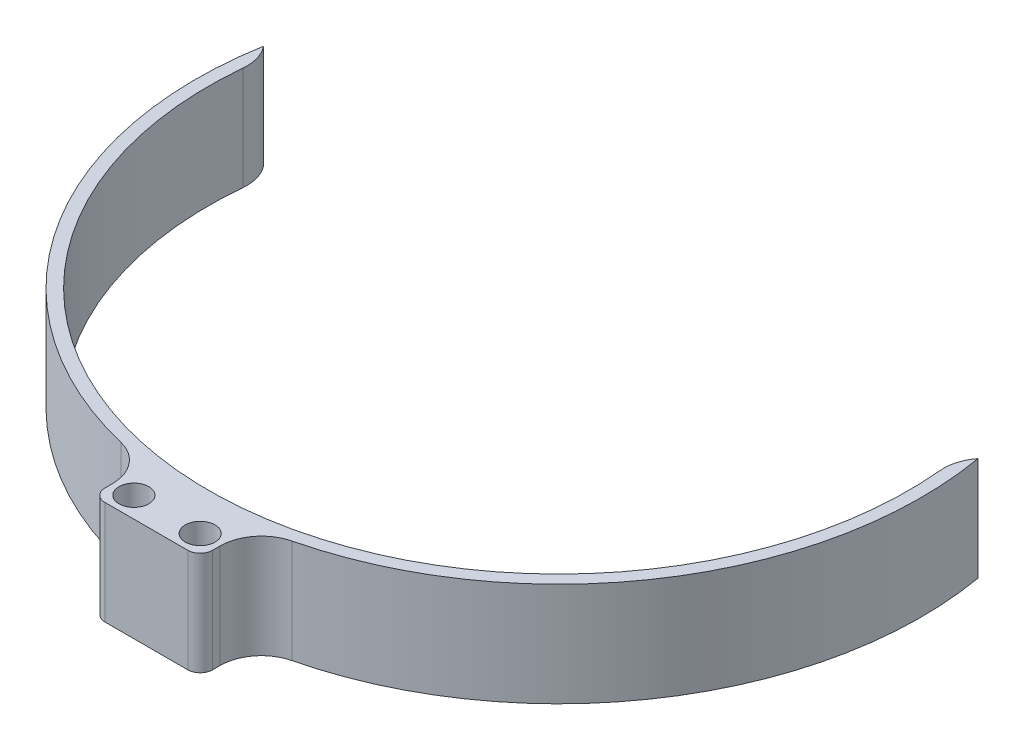
SolidWorks part; units mm, degrees
note: The reader was unsure of these and kept them because the rebuilt part matched: shared geometry of "草图1<8>".
ref_plane "前视基准面" through (0, 0, 0) normal (0, 0, 1) x (1, 0, 0)
ref_plane "上视基准面" through (0, 0, 0) normal (0, 1, 0) x (1, 0, 0)
ref_plane "右视基准面" through (0, 0, 0) normal (1, 0, 0) x (0, 0, -1)
sketch "草图1" plane through (0, 0, 5) normal (0, 1, 0) x (1, 0, 0)
  line L1 (-13, -81.5289) -> (-13, -94.5289)
  line L2 (-13, -94.5289) -> (13, -94.5289)
  line L5 (0, -50) -> (0, 60) construction
  line L9 (-86.2047, 20) -> (-83.158, 20)
  line L10 (83.158, 20) -> (86.2047, 20)
  line L11 (13, -81.5289) -> (13, -94.5289)
  arc A0 (-86.2047, 20) -> (86.2047, 20) centre (0, 5) ccw
  arc A1 (-83.158, 20) -> (83.158, 20) centre (0, 5) ccw
  arc A2 (86.2047, 20) -> (-86.2047, 20) centre (0, 5) ccw construction
  arc A3 (83.158, 20) -> (-83.158, 20) centre (0, 5) ccw construction
  circle A4 centre (-8, -89.5289) radius 2.3
  circle A5 centre (-8, -89.5289) radius 3.6
  circle A6 centre (8, -89.5289) radius 3.6
  circle A7 centre (8, -89.5289) radius 2.3
  dimension "D1" = 175
  dimension "D2" = 3
  dimension "D5" = 4.6
  dimension "D6" = 7.2
  dimension "D7" = 5
  dimension "D3" = 16
  dimension "D4" = 13
  dimension "D8" = 5
  dimension "D9" = 15
extrude "凸台-拉伸1" add sketch "草图1" along normal blind 5
extrude "凸台-拉伸2" add sketch "草图1<8>" along normal blind 20 from surface at 5
sketch "草图1<8>" plane through (0, 0, 5) normal (0, 1, 0) x (1, 0, 0) same geometry as "草图1"
fillet "圆角2" radius 10 4 edges at (-83.158, 12.5, -15) (83.158, 12.5, -15) (13, 12.5, 86.5289) (-13, 12.5, 86.5289)
fillet "圆角3" radius 3 2 edges at (13, 12.5, 99.5289) (-13, 12.5, 99.5289)
